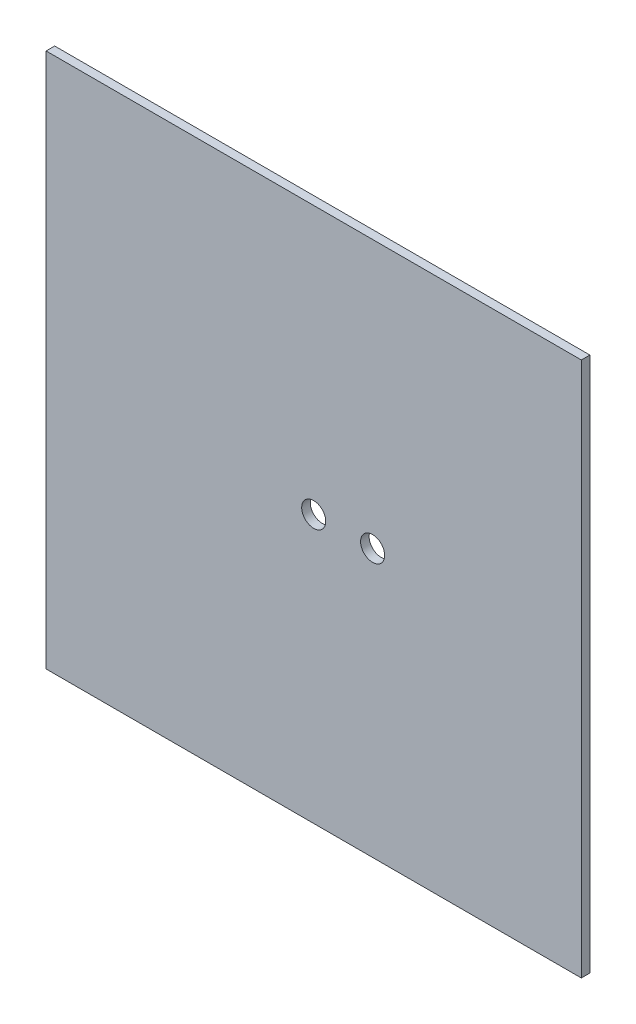
SolidWorks part; units mm, degrees
material "Copper"
ref_plane "Front Plane" through (0, 0, 0) normal (0, 0, 1) x (1, 0, 0)
ref_plane "Top Plane" through (0, 0, 0) normal (0, 1, 0) x (1, 0, 0)
ref_plane "Right Plane" through (0, 0, 0) normal (1, 0, 0) x (0, 0, -1)
sketch "Sketch1" plane through (0, 0, 0) normal (0, 0, 1) x (1, 0, 0)
  line L1 (-50, -50) -> (50, -50)
  line L2 (-50, -50) -> (-50, 50)
  line L3 (-50, 50) -> (50, 50)
  line L4 (50, -50) -> (50, 50)
  line L5 (-50, -50) -> (50, 50) construction
  line L6 (-50, 50) -> (50, -50) construction
  dimension "D1" = 100
extrude "Boss-Extrude1" add sketch "Sketch1" along normal blind 1.6
sketch "Sketch2" [suppressed] plane through (0, 0, 1.6) normal (0, 0, 1) x (1, 0, 0)
  circle A0 centre (0, 0) radius 50
  line M2 (50, -50) -> (50, 50)
  line M3 (50, 50) -> (-50, 50)
  line M4 (-50, 50) -> (-50, -50)
  line M5 (-50, -50) -> (50, -50)
  dimension "D1" = 100
extrude "Cut-Extrude1" [suppressed] cut sketch "Sketch2" against normal blind 1.6 contours A0 M3 M4 | A0 M4 M5 | A0 M5 M2 | A0 M2 M3
sketch "Sketch3" plane through (0, 0, 0) normal (0, 0, -1) x (-1, 0, 0)
  circle A0 centre (-11, 0) radius 2.25 construction
  circle A1 centre (-11, 0) radius 2.25
  circle A2 centre (0, 0) radius 2.2479 construction
  circle A3 centre (0, 0) radius 2.2479
extrude "Cut-Extrude2" cut sketch "Sketch3" against normal up to surface (1.6 mm away) up to face at (0, 0, 1.6)
